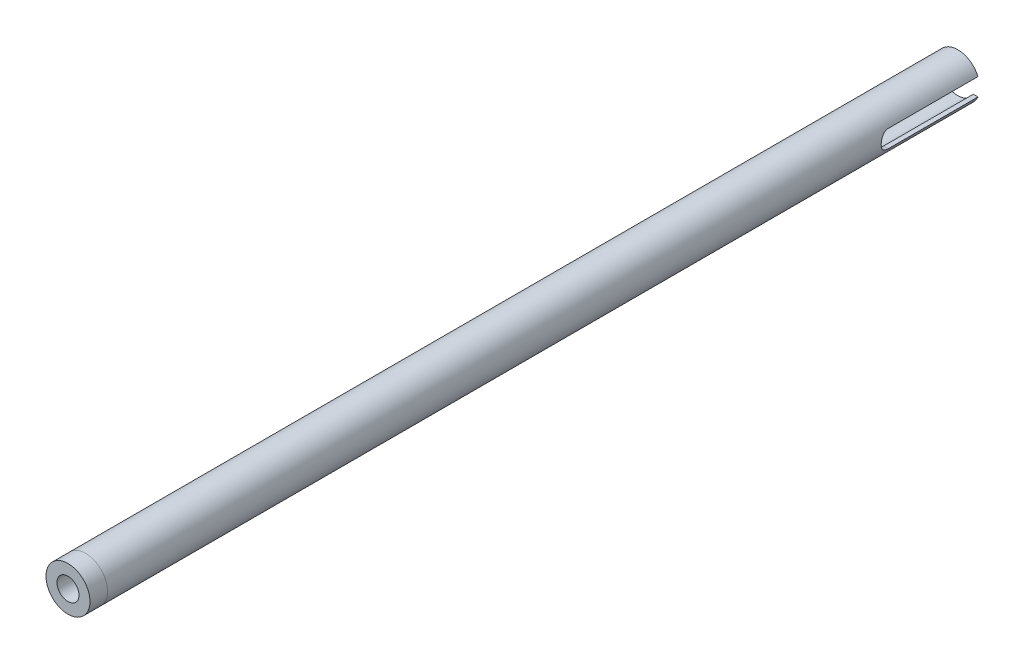
SolidWorks part; units mm, degrees
material "AISI 4130 Steel, annealed at 865C"
ref_plane "Front Plane" through (0, 0, 0) normal (0, 0, 1) x (1, 0, 0)
ref_plane "Top Plane" through (0, 0, 0) normal (0, 1, 0) x (1, 0, 0)
ref_plane "Right Plane" through (0, 0, 0) normal (1, 0, 0) x (0, 0, -1)
sketch "Axis" plane through (0, 0, 0) normal (0, 1, 0) x (1, 0, 0)
  line L0 (0, 0) -> (0, 320.8787) construction
  line L1 (0, 0) -> (0, -34.925) construction
  line L2 (0, 320.8787) -> (-7.9375, 320.8787) construction
  line L4 (0, 349.8508) -> (-25.9801, 255.0227) construction
  dimension "D1" = 34.925
  dimension "D2" = 7.9375
sketch "Sketch1" plane through (0, 0, 0) normal (0, 0, 1) x (1, 0, 0)
  line L0 (-7.9375, 0) -> (7.9375, 0) construction
  line L1 (-7.2748, 3.175) -> (7.2748, 3.175)
  line L2 (-7.2748, -3.175) -> (7.2748, -3.175)
  circle A0 centre (0, 0) radius 7.9375
  circle A1 centre (0, 0) radius 6.4135
  circle A2 centre (0, 0) radius 3.9688
  dimension "D1" = 15.875
  dimension "D3" = 7.9375
  dimension "D2" = 1.524
  dimension "D4" = 6.35
extrude "Threaded insert 1-1" add sketch "Sketch1" against normal blind 6.35 contours A2 L1 A1 | A1 L1 A0 | A2 L0 A1 L1 | A1 L0 A0 L1 | L0 A1 L2 A0 | L0 A2 L2 A1 | A2 L2 A1 | A1 L2 A0 | L0 A1 L2 A2 | L0 A0 L2 A1 | A0 L0 A1 L1 | A1 L0 A2 L1 region at (4.7887, 1.6543, 0) region at (4.7887, -1.6543, 0) region at (6.9234, 1.6163, 0) region at (6.9234, -1.6163, 0) region at (-4.7887, -1.6543, 0) region at (-4.7887, 1.6543, 0) region at (0, 4.6159, 0) region at (0, -4.6159, 0) region at (0, 6.5666, 0) region at (6.4237, -3.3281, 0) region at (-6.9234, -1.6163, 0) region at (-6.9234, 1.6163, 0)
extrude "Threaded insert 1-2" add sketch "Sketch1<3>" against normal blind 9.525 from surface contours A2 L1 A1 | A2 L0 A1 L1 | L0 A2 L2 A1 | A2 L2 A1 | L0 A1 L2 A2 | A1 L0 A2 L1 region at (4.7887, 1.6543, 0) region at (4.7887, -1.6543, 0) region at (-4.7887, -1.6543, 0) region at (-4.7887, 1.6543, 0) region at (0, 4.6159, 0) region at (0, -4.6159, 0) starting at face at (7.9375, 0, -6.35)
sketch "Sketch1<3>" plane through (0, 0, 0) normal (0, 0, 1) x (1, 0, 0) same geometry as "Sketch1"
extrude "A-arm tube" add sketch "Sketch1<4>" against normal up to vertex (320.8787 mm away) from surface separate body contours A1 L1 A0 | A1 L0 A0 L1 | L0 A1 L2 A0 | A1 L2 A0 | L0 A0 L2 A1 | A0 L0 A1 L1 region at (6.9234, 1.6163, 0) region at (6.9234, -1.6163, 0) region at (0, 6.5666, 0) region at (6.4237, -3.3281, 0) region at (-6.9234, -1.6163, 0) region at (-6.9234, 1.6163, 0) up to point (0, 0, -320.8787) starting at face at (6.4135, 0, -6.35)
sketch "Sketch1<4>" plane through (0, 0, 0) normal (0, 0, 1) x (1, 0, 0) same geometry as "Sketch1"
extrude "Apex slot" cut sketch "Sketch1<5>" along normal blind 35.56 from surface contours A0 L0 A1 L1 | L0 A0 L2 A1 | A1 L0 A0 L1 | L0 A1 L2 A0 region at (6.9234, 1.6163, 0) region at (6.9234, -1.6163, 0) region at (-6.9234, -1.6163, 0) region at (-6.9234, 1.6163, 0) starting at face at (6.4135, 0, -320.8787)
sketch "Sketch1<5>" plane through (0, 0, 0) normal (0, 0, 1) x (1, 0, 0) same geometry as "Sketch1"
fillet "Fillet1" radius 3.175 4 edges at (-6.4237, 3.175, -285.3187) (-6.4237, -3.175, -285.3187) (6.4237, -3.175, -285.3187) (6.4237, 3.175, -285.3187)
equation "\"tube diameter\"= 5 / 8"
equation "\"tube thickness\"= .06"
equation "\"apex thickness\"= .25"
equation "\"tube slot\"= 1.4"
equation "\"D1@Sketch1\"=\"tube diameter\""
equation "\"D2@Sketch1\"=\"tube thickness\""
equation "\"threaded insert hole\"= .3125"
equation "\"D3@Sketch1\"=\"threaded insert hole\""
equation "\"D4@Sketch1\"=\"apex thickness\""
equation "\"D1@Apex slot\" = \"tube slot\""
equation "\"D1@Fillet1\"=\"apex thickness\"/2"
equation "\"D2@Axis\"=\"tube diameter\"/2"
